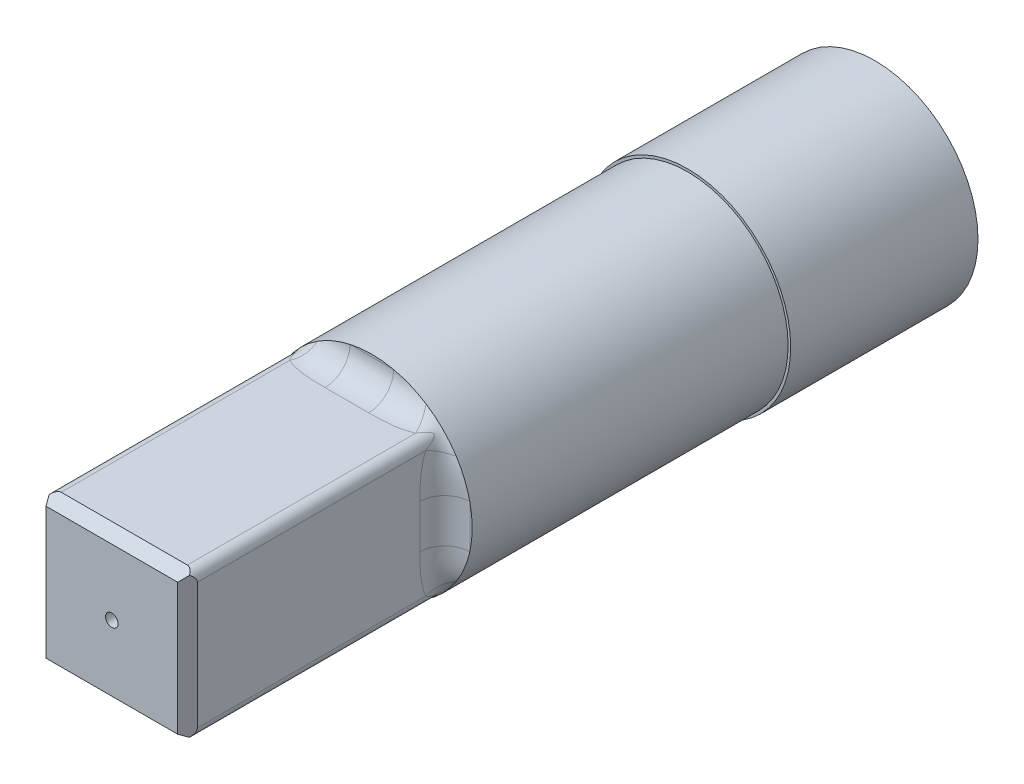
SolidWorks part; units mm, degrees
ref_plane "Front Plane" through (0, 0, 0) normal (0, 0, 1) x (1, 0, 0)
ref_plane "Top Plane" through (0, 0, 0) normal (0, 1, 0) x (1, 0, 0)
ref_plane "Right Plane" through (0, 0, 0) normal (1, 0, 0) x (0, 0, -1)
sketch "Sketch1" plane through (0, 0, 0) normal (0, 0, 1) x (1, 0, 0)
  line L1 (1.862, 3.225) -> (-1.862, 3.225)
  line L2 (-1.862, 3.225) -> (-3.7239, 0)
  line L3 (-3.7239, 0) -> (-1.862, -3.225)
  line L4 (-1.862, -3.225) -> (1.862, -3.225)
  line L5 (1.862, -3.225) -> (3.7239, 0)
  line L6 (3.7239, 0) -> (1.862, 3.225)
  line L7 (-5.85, -5.85) -> (5.85, -5.85)
  line L8 (-5.85, -5.85) -> (-5.85, 5.85)
  line L9 (-5.85, 5.85) -> (5.85, 5.85)
  line L10 (5.85, -5.85) -> (5.85, 5.85)
  line L11 (-5.85, -5.85) -> (5.85, 5.85) construction
  line L12 (-5.85, 5.85) -> (5.85, -5.85) construction
  circle A0 centre (0, 0) radius 3.225 construction
  dimension "D1" = 11.7
  dimension "D2" = 6.45
extrude "Boss-Extrude1" add sketch "Sketch1" along normal blind 46.12
chamfer "Chamfer1" [suppressed] distance 1 angle 45
chamfer "Chamfer2" distance 1 angle 30 4 edges at (0, -5.85, 46.12) (-5.85, 0, 46.12) (5.85, 0, 46.12) (0, 5.85, 46.12) first distance on face at (0, -5.85, 23.06) first distance on face at (-5.85, 0, 23.06) first distance on face at (5.85, 0, 23.06) first distance on face at (0, 5.85, 23.06)
fillet "Fillet1" radius 0.8 4 edges at (-5.85, -5.85, 22.56) (5.85, -5.85, 22.56) (5.85, 5.85, 22.56) (-5.85, 5.85, 22.56)
sketch "Sketch2" plane through (0, 0, 0) normal (0, 0, 1) x (1, 0, 0)
  circle A0 centre (0, 0) radius 3.7239
  circle A1 centre (0, 0) radius 7.9418 construction
  arc A2 (5.6157, 5.6157) -> (5.05, 5.85) centre (5.05, 5.05) ccw construction
  circle A3 centre (0, 0) radius 8.0418
  dimension "D1" = 0.1
extrude "Boss-Extrude2" add sketch "Sketch2" along normal blind 25.3
sketch "Sketch5" plane through (0, 0, 0) normal (0, 0, -1) x (-1, 0, 0)
  line L0 (3.7239, 0) -> (1.862, -3.225) construction
  line L1 (1.862, -3.225) -> (-1.862, -3.225) construction
  line L2 (-1.862, -3.225) -> (-3.7239, 0) construction
  line L3 (1.862, 3.225) -> (3.7239, 0) construction
  line L4 (-1.862, 3.225) -> (1.862, 3.225) construction
  line L5 (-3.7239, 0) -> (-1.862, 3.225) construction
  line L6 (3.7239, 0) -> (1.862, -3.225)
  line L7 (1.862, -3.225) -> (-1.862, -3.225)
  line L8 (-1.862, -3.225) -> (-3.7239, 0)
  line L9 (1.862, 3.225) -> (3.7239, 0)
  line L10 (-1.862, 3.225) -> (1.862, 3.225)
  line L11 (-3.7239, 0) -> (-1.862, 3.225)
  circle A2 centre (0, 0) radius 8.25
  dimension "D2" = 16.5
extrude "Boss-Extrude5" add sketch "Sketch5" along normal blind 15
sketch "Sketch3" plane through (0, 0, 46.12) normal (0, 0, 1) x (1, 0, 0)
  circle A0 centre (0, 0) radius 3.7239
extrude "Boss-Extrude3" add sketch "Sketch3" against normal offset from surface (36.12 mm away) 25 up to face at (-8.25, 0, -15)
fillet "Fillet2" radius 2 4 edges at (5.85, 0, 25.3) (0, -5.85, 25.3) (-5.85, 0, 25.3) (0, 5.85, 25.3)
sketch "Sketch6" plane through (0, 0, 0) normal (0, 0, 1) x (1, 0, 0)
  circle A0 centre (0, 0) radius 0.5
  dimension "D1" = 1
extrude "Cut-Extrude2" cut sketch "Sketch6" along normal through all
